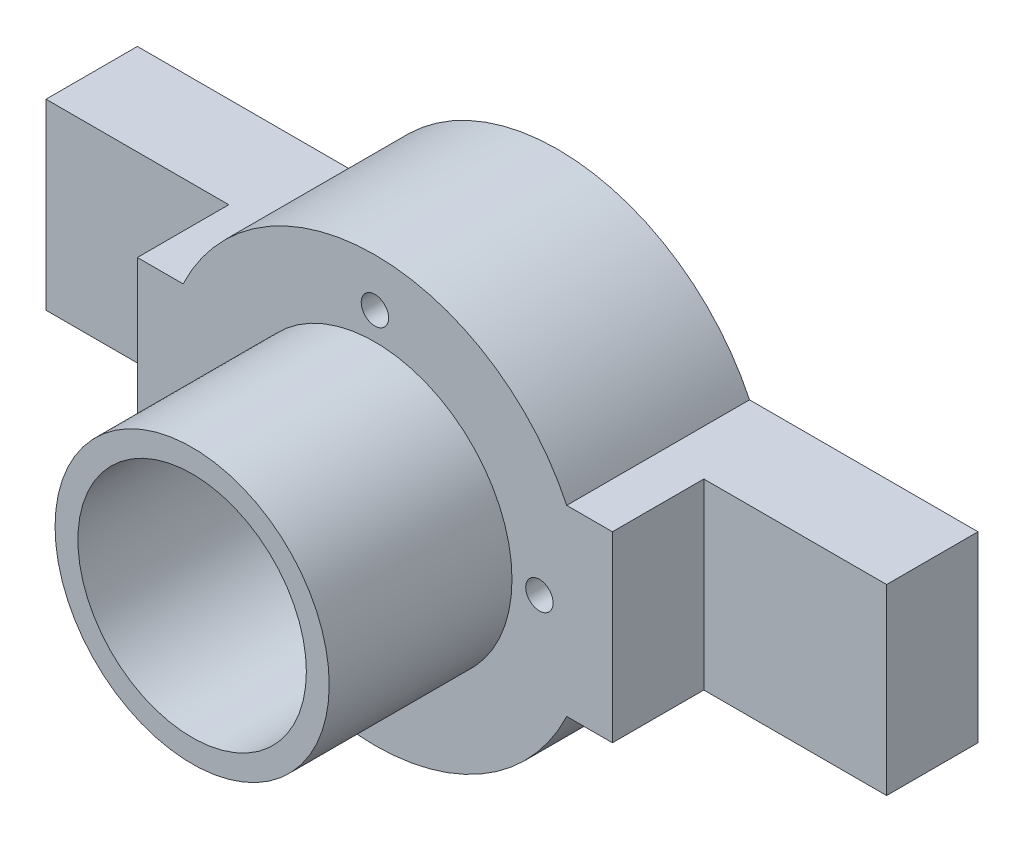
SolidWorks part; units mm, degrees
ref_plane "Alzado" through (0, 0, 0) normal (0, 0, 1) x (1, 0, 0)
ref_plane "Planta" through (0, 0, 0) normal (0, 1, 0) x (1, 0, 0)
ref_plane "Vista lateral" through (0, 0, 0) normal (1, 0, 0) x (0, 0, -1)
sketch "Croquis1" plane through (0, 0, 0) normal (0, 0, 1) x (1, 0, 0)
  circle A0 centre (0, 0) radius 15
  circle A1 centre (0, 0) radius 12.5
  dimension "D1" = 30
  dimension "D2" = 25
extrude "Saliente-Extruir1" add sketch "Croquis1" against normal blind 20
sketch3d "Croquis3D3"
  line L0 (0, 0, 0) -> (0, 0, -60) construction
  line L1 (0, 0, -60) -> (40, 0, -60) construction
  line L2 (40, 0, -60) -> (40, 0, -35) construction
  line L3 (40, 0, -35) -> (0, 0, -35) construction
  line L4 (0, 0, -35) -> (-40, 0, -35) construction
  line L5 (-40, 0, -35) -> (-40, 0, -60.0108) construction
  line L6 (-40, 0, -60.0108) -> (0, 0, -60) construction
  line L7 (0, 0, -35) -> (-46.9846, -17.101, -35) construction
  line L8 (0, 0, -35) -> (46.9846, -17.101, -35) construction
  line L9 (0, 0, 0) -> (0, -10.0221, 0) construction
  line L10 (46.9846, -17.101, -35) -> (46.9846, 0, -35) construction
  line L11 (-46.9846, -17.101, -35) -> (-46.9846, 0, -35) construction
  dimension "D2" = 25
  dimension "D1" = 60
  dimension "D3" = 40
  dimension "D4" = 140
  dimension "D5" = 50
sketch "Croquis8" plane through (0, 0, -20) normal (0, 0, -1) x (-1, 0, 0)
  line L0 (0, 0) -> (0, 18) construction
  line L1 (0, 0) -> (-18, 0) construction
  line L2 (0, 0) -> (-40, 0) construction
  line L3 (0, 0) -> (0, -18) construction
  line L4 (0, 0) -> (18, 0) construction
  line L5 (0, 0) -> (40, 0) construction
  circle A0 centre (0, 0) radius 23.25
  circle A1 centre (0, 18) radius 1.5
  circle A2 centre (18, 0) radius 1.5
  circle A3 centre (0, -18) radius 1.5
  circle A4 centre (-18, 0) radius 1.5
  dimension "D1" = 46.5
  dimension "D3" = 3
  dimension "D2" = 18
extrude "Saliente-Extruir2" add sketch "Croquis8" along normal blind 20
sketch "Croquis10" plane through (0, 0, -40) normal (0, 0, -1) x (-1, 0, 0)
  line L0 (20.9896, 0) -> (-20.9896, 0) construction
  line L1 (-20.9896, 10) -> (-20.9896, -10) construction
  line L2 (-20.9896, 10) -> (-45.9896, 10)
  line L3 (-45.9896, 10) -> (-45.9896, -10)
  line L4 (-45.9896, -10) -> (-20.9896, -10)
  line L5 (-20.9896, -10) -> (-20.9896, 10)
  line L6 (0, 0) -> (0, 10) construction
  line L7 (45.9896, -10) -> (20.9896, -10)
  line L8 (45.9896, 10) -> (45.9896, -10)
  line L9 (20.9896, 10) -> (45.9896, 10)
  line L10 (20.9896, -10) -> (20.9896, 10)
  circle A0 centre (0, 0) radius 23.25 construction
  point P5 (0, 0)
  point P11 (-20.9896, 0)
  dimension "D1" = 20
  dimension "D2" = 25
extrude "Saliente-Extruir6" add sketch "Croquis10" against normal blind 20
sketch "Croquis11" plane through (0, 0, -20) normal (0, 0, -1) x (-1, 0, 0)
  line L0 (-45.9896, 10) -> (-25.9896, 10)
  line L1 (-20.9896, 10) -> (-45.9896, 10) construction
  line L2 (-25.9896, 10) -> (-25.9896, -10)
  line L3 (-45.9896, -10) -> (-20.9896, -10) construction
  line L4 (-25.9896, -10) -> (-45.9896, -10)
  line L5 (-45.9896, -10) -> (-45.9896, 10)
  line L6 (0, 0) -> (0, 8.6178) construction
  line L7 (25.9896, -10) -> (45.9896, -10)
  line L8 (25.9896, 10) -> (25.9896, -10)
  line L9 (45.9896, 10) -> (25.9896, 10)
  line L10 (45.9896, -10) -> (45.9896, 10)
  dimension "D1" = 20
extrude "Cortar-Extruir2" cut sketch "Croquis11" along normal blind 10
